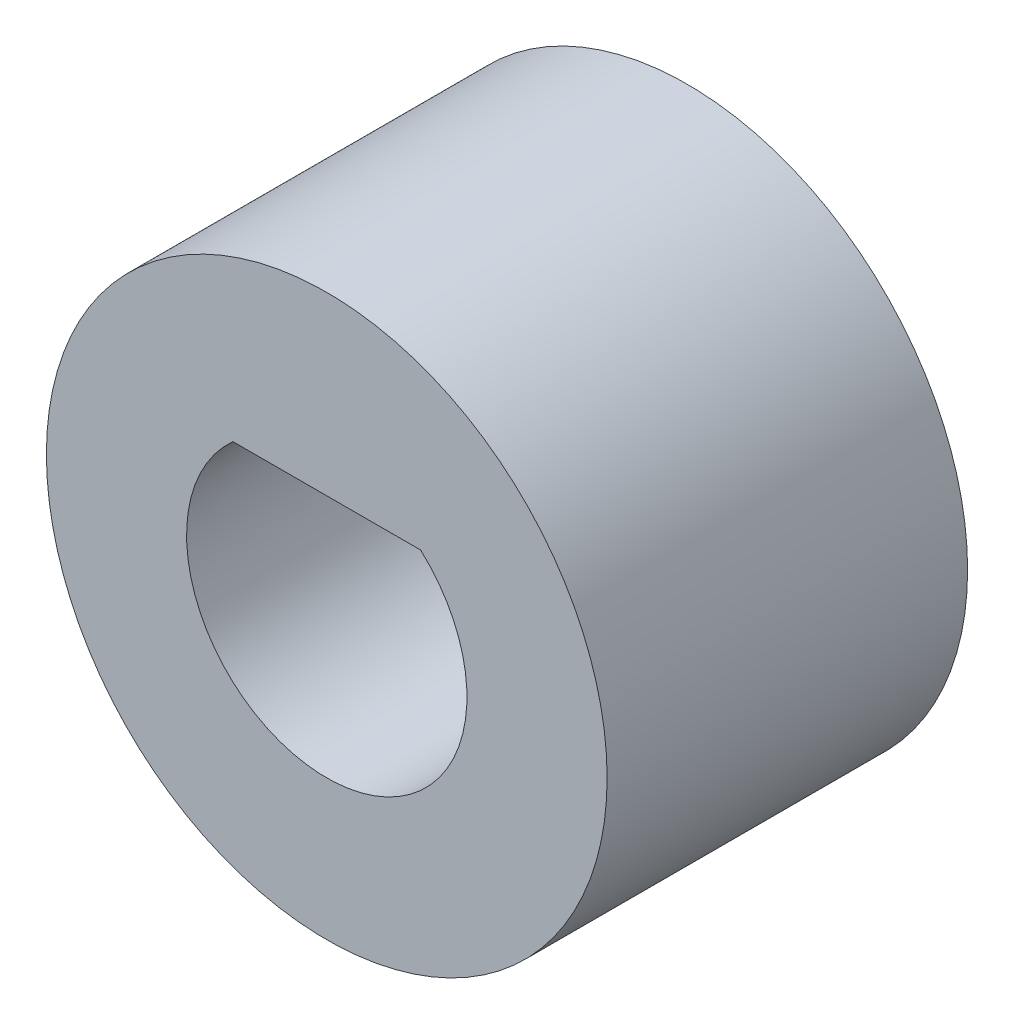
SolidWorks part; units mm, degrees
ref_plane "Plan de face" through (0, 0, 0) normal (0, 0, 1) x (1, 0, 0)
ref_plane "Plan de dessus" through (0, 0, 0) normal (0, 1, 0) x (1, 0, 0)
ref_plane "Plan de droite" through (0, 0, 0) normal (1, 0, 0) x (0, 0, -1)
sketch "Esquisse1" plane through (0, 0, 0) normal (0, 0, 1) x (1, 0, 0)
  line L0 (-2.3431, 2.6) -> (2.3431, 2.6)
  line L1 (-0.9885, -3.5) -> (1.037, -3.5) construction
  circle A0 centre (0, 0) radius 7
  arc A1 (-2.3431, 2.6) -> (2.3431, 2.6) centre (0, 0) ccw
  dimension "D1" = 14
  dimension "D2" = 7
  dimension "D3" = 6.1
extrude "Boss.-Extru.1" add sketch "Esquisse1" along normal blind 9
